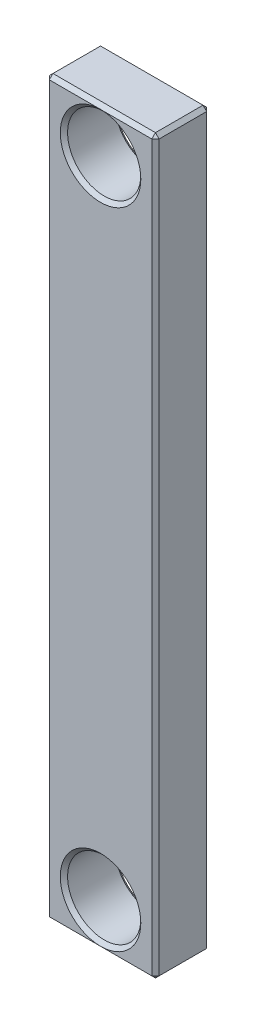
SolidWorks part; units mm, degrees
ref_plane "Front Plane" through (0, 0, 0) normal (0, 0, 1) x (1, 0, 0)
ref_plane "Top Plane" through (0, 0, 0) normal (0, 1, 0) x (1, 0, 0)
ref_plane "Right Plane" through (0, 0, 0) normal (1, 0, 0) x (0, 0, -1)
sketch "Sketch1" plane through (0, 0, 0) normal (0, 0, 1) x (1, 0, 0)
  line L1 (-15, 100) -> (15, 100)
  line L2 (-15, 100) -> (-15, -100)
  line L3 (-15, -100) -> (15, -100)
  line L4 (15, 100) -> (15, -100)
  line L5 (-15, 100) -> (15, -100) construction
  line L6 (-15, -100) -> (15, 100) construction
  circle A0 centre (0, 88) radius 10
  circle A1 centre (0, -88) radius 10
  point P0 (0, 0)
  dimension "D3" = 20
  dimension "D4" = 20
  dimension "D1" = 200
  dimension "D2" = 30
  dimension "D5" = 12
  dimension "D6" = 12
extrude "Boss-Extrude1" add sketch "Sketch1" along normal blind 15
chamfer "Chamfer1" distance 1 angle 45 16 edges at (15, 100, 7.5) (-15, 100, 7.5) (-15, -100, 7.5) (0, -100, 15) (-15, 0, 15) (0, 100, 15) (15, 0, 15) (15, -100, 7.5) (0, -100, 0) (-15, 0, 0) (0, 100, 0) (15, 0, 0) (10, 88, 15) (10, 88, 0) (10, -88, 15) (10, -88, 0)
